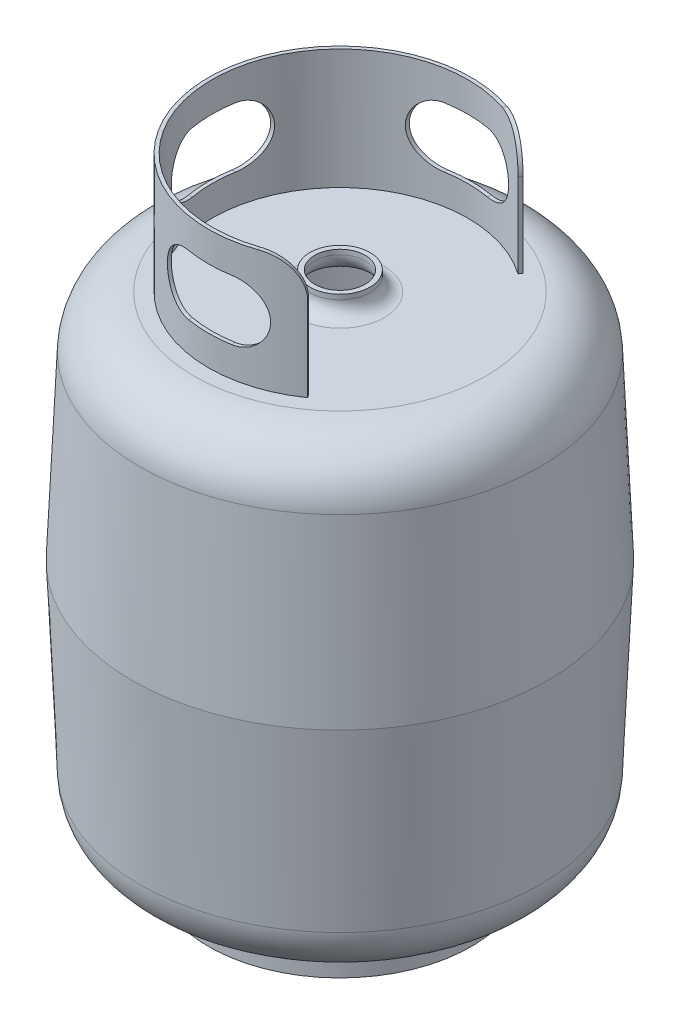
SolidWorks part; units mm, degrees
material "1060 Alloy"
ref_plane "Front Plane" through (0, 0, 0) normal (0, 0, 1) x (1, 0, 0)
ref_plane "Top Plane" through (0, 0, 0) normal (0, 1, 0) x (1, 0, 0)
ref_plane "Right Plane" through (0, 0, 0) normal (1, 0, 0) x (0, 0, -1)
sketch "Sketch1" plane through (0, 0, 0) normal (0, 0, 1) x (1, 0, 0)
  line L0 (0, 287.6116) -> (0, -281.3761) construction
  line L1 (-424.0127, 0) -> (428.6893, 0) construction
  line L2 (0, -193.75) -> (-121.539, -193.75)
  line L3 (-166.4962, -150.7129) -> (-173.0765, 0)
  line L4 (-173.0765, 0) -> (-166.4962, 150.7129)
  line L5 (-121.539, 193.75) -> (-37, 193.75)
  line L6 (-25, 205.75) -> (-25, 209.75)
  line L7 (0, -189.75) -> (-121.539, -189.75)
  line L8 (-162.5, -150.5384) -> (-169.0726, 0)
  line L9 (-169.0726, 0) -> (-162.5, 150.5384)
  line L10 (-121.539, 189.75) -> (-37, 189.75)
  line L11 (-21, 205.75) -> (-21, 209.75)
  line L12 (-25, 209.75) -> (-21, 209.75)
  line L13 (0, -189.75) -> (0, -193.75)
  line L14 (-162.5, 150.5384) -> (-162.5, 193.75) construction
  arc A0 (-37, 193.75) -> (-25, 205.75) centre (-37, 205.75) ccw
  arc A1 (-121.539, -193.75) -> (-166.4962, -150.7129) centre (-121.539, -148.75) cw
  arc A2 (-166.4962, 150.7129) -> (-121.539, 193.75) centre (-121.539, 148.75) cw
  arc A3 (-121.539, -189.75) -> (-162.5, -150.5384) centre (-121.539, -148.75) cw
  arc A4 (-162.5, 150.5384) -> (-121.539, 189.75) centre (-121.539, 148.75) cw
  arc A5 (-37, 189.75) -> (-21, 205.75) centre (-37, 205.75) ccw
  dimension "D4" = 12
  dimension "D5" = 45
  dimension "D1" = 387.5
  dimension "D2" = 92.5
  dimension "D3" = 92.5
  dimension "D6" = 50
  dimension "D8" = 20
  dimension "D9" = 325
  dimension "D7" = 4
revolve "Revolve1" add sketch "Sketch1" angle 360 about L0
sketch "Sketch4" plane through (0, 193.75, 0) normal (0, 1, 0) x (1, 0, 0)
  line L0 (0, 0) -> (121.539, 0) construction
  line L1 (0, 0) -> (69.7119, 99.5589) construction
  line L2 (0, 0) -> (69.7119, -99.5589) construction
  line L3 (62.829, 89.7291) -> (61.1083, 87.2717)
  line L4 (61.1083, -87.2717) -> (62.829, -89.7291)
  arc A0 (62.829, 89.7291) -> (62.829, -89.7291) centre (0, 0) ccw
  circle A1 centre (0, 0) radius 121.539 construction
  arc A2 (61.1083, 87.2717) -> (61.1083, -87.2717) centre (0, 0) ccw
  circle A3 centre (0, 0) radius 109.539 construction
  circle A4 centre (0, 0) radius 106.539 construction
  dimension "D1" = 12
  dimension "D3" = 55
  dimension "D2" = 3
sketch "Sketch6" plane through (0, -193.75, 0) normal (0, -1, 0) x (1, 0, 0)
  circle A0 centre (0, 0) radius 109.539
  circle A1 centre (0, 0) radius 121.539 construction
  circle A2 centre (0, 0) radius 106.539
  dimension "D1" = 12
  dimension "D2" = 3
extrude "Boss-Extrude3" add sketch "Sketch6" along normal blind 30
sketch "Sketch7" plane through (0, 193.75, 0) normal (0, 1, 0) x (1, 0, 0)
  line L0 (69.7119, 99.5589) -> (0, 0) construction
  line L1 (0, 0) -> (121.539, 0) construction
  line L2 (69.7119, -99.5589) -> (0, 0) construction
  line L3 (62.829, 89.7291) -> (61.1083, 87.2717)
  line L4 (61.1083, -87.2717) -> (62.829, -89.7291)
  arc A0 (62.829, 89.7291) -> (62.829, -89.7291) centre (0, 0) ccw
  circle A1 centre (0, 0) radius 121.539 construction
  arc A2 (61.1083, 87.2717) -> (61.1083, -87.2717) centre (0, 0) ccw
  circle A3 centre (0, 0) radius 106.539 construction
  circle A4 centre (0, 0) radius 109.539 construction
  dimension "D1" = 12
  dimension "D3" = 55
  dimension "D2" = 3
extrude "Boss-Extrude4" add sketch "Sketch7" along normal blind 100
sketch "Sketch8" plane through (0, 0, 0) normal (0, 0, 1) x (1, 0, 0)
  line L0 (0, 0) -> (0, 293.75) construction
  line L1 (61.1083, 293.75) -> (-106.539, 293.75) construction
  line L2 (-18, 243.75) -> (18, 243.75) construction
  line L3 (-18, 268.75) -> (18, 268.75)
  line L4 (-18, 218.75) -> (18, 218.75)
  line L5 (62.829, 293.75) -> (-109.539, 293.75) construction
  arc A0 (-18, 268.75) -> (-18, 218.75) centre (-18, 243.75) ccw
  arc A1 (18, 218.75) -> (18, 268.75) centre (18, 243.75) ccw
  point P7 (0, 243.75)
  dimension "D1" = 50
  dimension "D2" = 50
  dimension "D3" = 18
extrude "Cut-Extrude4" cut sketch "Sketch8" against normal through all
pattern_circular "CirPattern3" count 3 over 180 about axis through (0, 293.75, 0) along (0, -1, 0) of "Cut-Extrude4" reverse direction yes
fillet "Fillet4" radius 30 2 edges at (61.9686, 293.75, 88.5004) (61.9686, 293.75, -88.5004)
equation "\"A\"= 325mm"
equation "\"B\"= 387.5mm"
equation "\"D1@Sketch1\"=\"B\""
equation "\"D9@Sketch1\"=\"A\""
